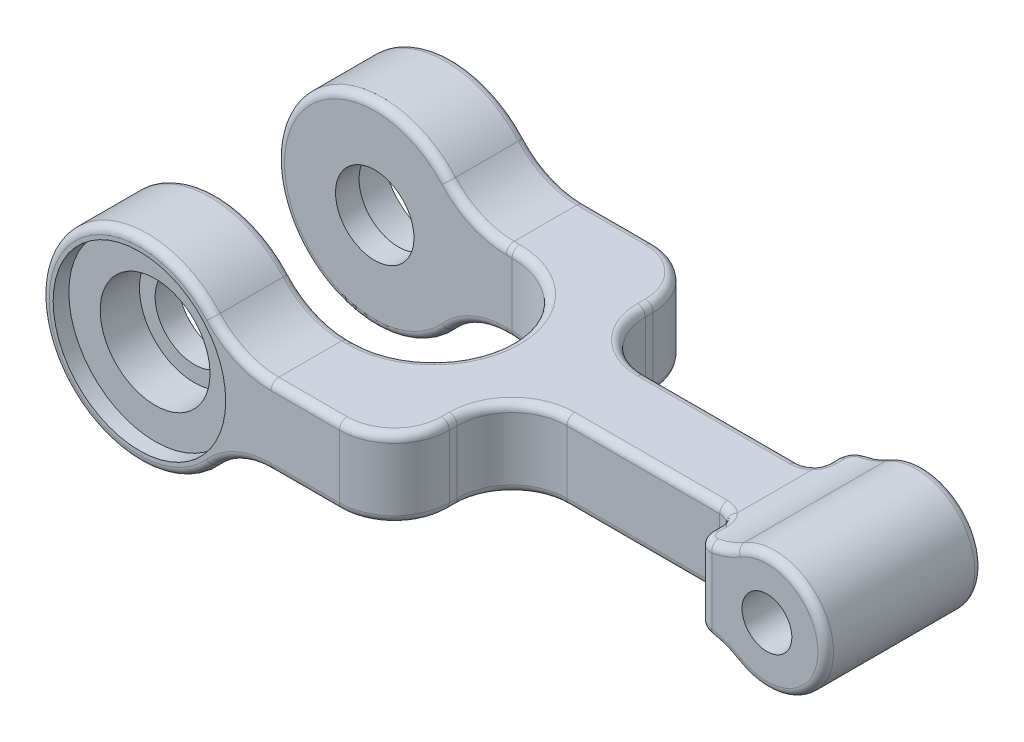
SolidWorks part; units mm, degrees
ref_plane "Front Plane" through (0, 0, 0) normal (0, 0, 1) x (1, 0, 0)
ref_plane "Top Plane" through (0, 0, 0) normal (0, 1, 0) x (1, 0, 0)
ref_plane "Right Plane" through (0, 0, 0) normal (1, 0, 0) x (0, 0, -1)
sketch "Sketch1" plane through (0, 0, 0) normal (0, 0, 1) x (1, 0, 0)
  line L0 (0, 5) -> (0, -5) construction
  line L1 (-18.2295, 5) -> (25.9861, 5)
  line L3 (-18.2295, -5) -> (25.9861, -5)
  line L5 (-35, 0) -> (35, 0) construction
  arc A0 (-25.6831, 8.3333) -> (-25.6831, -8.3333) centre (-35, 0) ccw
  arc A1 (31.1369, -6.4286) -> (31.1369, 6.4286) centre (35, 0) ccw
  arc A2 (25.9861, 5) -> (31.1369, 6.4286) centre (25.9861, 15) ccw
  arc A3 (25.9861, -5) -> (31.1369, -6.4286) centre (25.9861, -15) cw
  arc A4 (-25.6831, -8.3333) -> (-18.2295, -5) centre (-18.2295, -15) cw
  arc A5 (-18.2295, 5) -> (-25.6831, 8.3333) centre (-18.2295, 15) cw
  dimension "D3" = 25
  dimension "D4" = 15
  dimension "D5" = 10
  dimension "D1" = 10
  dimension "D2" = 70
extrude "Boss-Extrude1" add sketch "Sketch1" along normal mid plane 40
sketch "Sketch2" plane through (0, 0, 0) normal (0, 1, 0) x (1, 0, 0)
  line L0 (-47.5, 20) -> (-47.5, -20) construction
  line L1 (-47.5, 10) -> (-17.5, 10)
  line L2 (-47.5, 10) -> (-47.5, -10)
  line L3 (-47.5, -10) -> (-17.5, -10)
  line L5 (-47.5, 0) -> (0, 0) construction
  arc A0 (-17.5, -10) -> (-17.5, 10) centre (-17.5, 0) ccw
  dimension "D1" = 20
  dimension "D2" = 30
extrude "Cut-Extrude1" cut sketch "Sketch2" against normal through all and the other way through all
sketch "Sketch3" plane through (0, 0, 0) normal (0, 1, 0) x (1, 0, 0)
  line L0 (42.5, 10) -> (25.9861, 10)
  line L1 (42.5, -20) -> (42.5, 20) construction
  line L2 (25.9861, 10) -> (25.9861, 5)
  line L3 (25.9861, 5) -> (-2.5, 5)
  line L5 (-2.5, 5) -> (-2.5, 20)
  line L6 (-2.5, 20) -> (42.5, 20)
  line L7 (42.5, 20) -> (42.5, 10)
  line L8 (-37.32, 0) -> (53.9836, 0) construction
  line L9 (42.5, -20) -> (42.5, -10)
  line L10 (42.5, -10) -> (25.9861, -10)
  line L11 (25.9861, -10) -> (25.9861, -5)
  line L12 (-2.5, -20) -> (42.5, -20)
  line L13 (25.9861, -5) -> (-2.5, -5)
  line L14 (-2.5, -5) -> (-2.5, -20)
  line L15 (42.5, 20) -> (31.1369, 20) construction
  line L16 (25.9861, -20) -> (25.9861, 20) construction
  arc A0 (-17.5, -10) -> (-17.5, 10) centre (-17.5, 0) ccw construction
  dimension "D3" = 15
  dimension "D1" = 10
  dimension "D2" = 20
extrude "Cut-Extrude2" cut sketch "Sketch3" against normal through all and the other way through all
sketch "Sketch4" plane through (0, 0, -20) normal (0, 0, -1) x (-1, 0, 0)
  circle A0 centre (35, 0) radius 5
  arc A1 (25.6831, -8.3333) -> (25.6831, 8.3333) centre (35, 0) ccw construction
  dimension "D1" = 10
extrude "Cut-Extrude3" cut sketch "Sketch4" against normal up to next
sketch "Sketch5" plane through (0, 0, -20) normal (0, 0, -1) x (-1, 0, 0)
  circle A0 centre (35, 0) radius 7
  circle A1 centre (35, 0) radius 5 construction
  dimension "D1" = 2
extrude "Cut-Extrude4" cut sketch "Sketch5" against normal blind 7
sketch "Sketch6" plane through (0, 0, -20) normal (0, 0, -1) x (-1, 0, 0)
  circle A0 centre (35, 0) radius 11
  circle A3 centre (35, 0) radius 7 construction
  dimension "D1" = 4
extrude "Cut-Extrude5" cut sketch "Sketch6" against normal blind 2
sketch "Sketch7" plane through (0, 0, -10) normal (0, 0, -1) x (-1, 0, 0)
  circle A0 centre (-35, 0) radius 3.175
  arc A1 (-31.1369, 6.4286) -> (-31.1369, -6.4286) centre (-35, 0) ccw construction
  dimension "D1" = 6.35
extrude "Cut-Extrude6" cut sketch "Sketch7" against normal through all
mirror "Mirror1" about plane through (0, 0, 0) normal (0, 0, 1) of "Cut-Extrude3", "Cut-Extrude4", "Cut-Extrude5"
fillet "Fillet6" radius 7 4 edges at (-2.5, 0, -20) (-2.5, 0, -5) (-2.5, 0, 5) (-2.5, 0, 20)
fillet "Fillet7" radius 2 4 edges at (25.9861, 0, -10) (25.9861, 0, -5) (25.9861, 0, 5) (25.9861, 0, 10)
fillet "Fillet8" radius 1 44 edges at (25.4003, 5, -5.5858) (25.9861, 5, -7.5) (26.7477, 5.029, -9.5705) (29.6137, 5.6812, -10) (42.5, 0, -10) (29.6137, -5.6812, -10) (26.4241, -5.0096, -9.249) (25.9861, -5, -7.5) (25.4003, -5, -5.5858) (14.2431, -5, -5) (-0.4497, -5, -7.0503) (-2.5, -5, -12.5) (-4.5503, -5, -17.9497) (-13.8647, -5, -20) (-22.312, -5.8713, -20) (-47.5, 0, -20) (-22.312, 5.8713, -20) (-13.8647, 5, -20) (-4.5503, 5, -17.9497) (-2.5, 5, -12.5) (-0.4497, 5, -7.0503) (-4.5503, 5, 17.9497) (-2.5, 5, 12.5) (-0.4497, 5, 7.0503) (14.2431, 5, 5) (25.4003, 5, 5.5858) (25.9861, 5, 7.5) (26.4241, 5.0096, 9.249) (29.6137, 5.6812, 10) (42.5, 0, 10) (29.6137, -5.6812, 10) (26.7477, -5.029, 9.5705) (25.9861, -5, 7.5) (25.4003, -5, 5.5858) (14.2431, -5, 5) (-0.4497, -5, 7.0503) (-2.5, -5, 12.5) (-4.5503, -5, 17.9497) (-13.8647, -5, 20) (-22.312, -5.8713, 20) (-47.5, 0, 20) (-22.312, 5.8713, 20) (14.2431, 5, -5) (-13.8647, 5, 20)
fillet "Fillet9" radius 1 12 edges at (-17.8647, 5, -10) (-22.312, 5.8713, -10) (-47.5, 0, -10) (-22.312, -5.8713, -10) (-17.8647, -5, -10) (-7.5, -5, 0) (-17.8647, -5, 10) (-22.312, -5.8713, 10) (-47.5, 0, 10) (-22.312, 5.8713, 10) (-17.8647, 5, 10) (-7.5, 5, 0)
